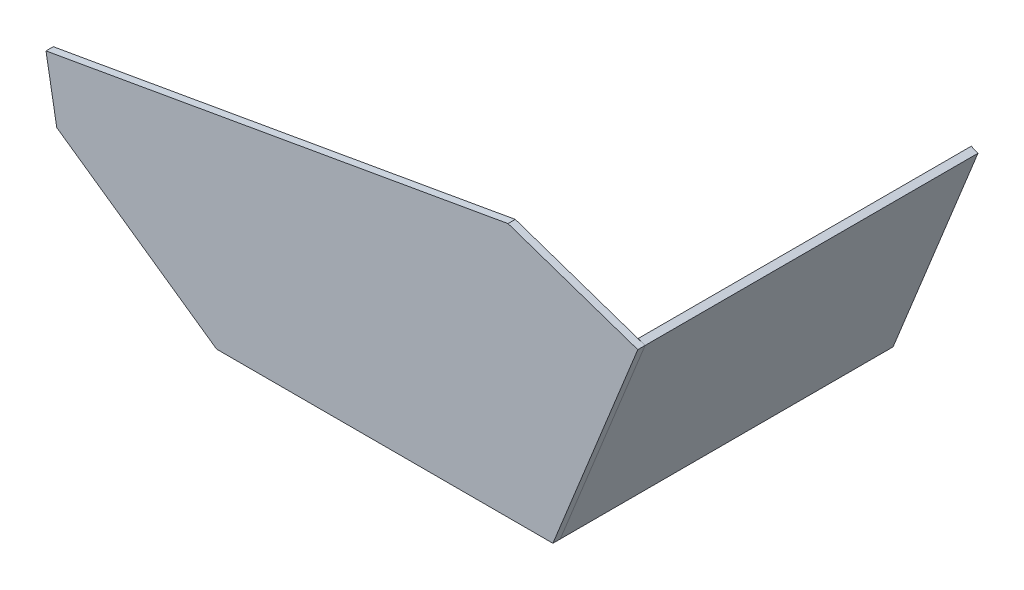
SolidWorks part; units mm, degrees
material "Melamine"
ref_plane "Front Plane" through (0, 0, 0) normal (0, 0, 1) x (1, 0, 0)
ref_plane "Top Plane" through (0, 0, 0) normal (0, 1, 0) x (1, 0, 0)
ref_plane "Right Plane" through (0, 0, 0) normal (1, 0, 0) x (0, 0, -1)
ref_axis "Axis1" through (0, 0, -14.8175) along (0, 0, 1)
sketch "Sketch1" plane through (0, 0, 0) normal (0, 0, 1) x (1, 0, 0)
  line L0 (-137.5, 0) -> (137.5, 0) construction
  line L1 (-137.5, 0) -> (-301.3304, 114.7153) construction
  line L4 (-148.5709, 0) -> (-304.9726, 109.5137) construction
  line L5 (-304.9726, 109.5137) -> (-301.3304, 114.7153) construction
  line L11 (137.5, 0) -> (144.3487, 0)
  line L12 (137.5, 0) -> (212.4213, 185.4368) construction
  line L14 (144.3487, 0) -> (218.3089, 183.058)
  line L15 (218.3089, 183.058) -> (212.4213, 185.4368)
  line L16 (212.4213, 185.4368) -> (137.5, 0)
  line L17 (-137.5, 0) -> (-148.5709, 0) construction
  point P4 (0, 0)
  dimension "D1" = 35
  dimension "D2" = 275
  dimension "D4" = 200
  dimension "D6" = 6.35
  dimension "D7" = 68
  dimension "D8" = 200
  dimension "D9" = 6.35
extrude "Boss-Extrude1" add sketch "Sketch1" along normal blind 290
sketch "Sketch2" plane through (0, 0, 290) normal (0, 0, 1) x (1, 0, 0)
  line L1 (-297.2025, 150.6805) -> (105.2664, 221.6466)
  line L3 (144.3487, 0) -> (-148.5709, 0)
  line L4 (-148.5709, 0) -> (-287.8267, 97.508) construction
  line L5 (144.3487, 0) -> (218.3089, 183.058)
  line L7 (-287.8267, 97.508) -> (-297.2025, 150.6805)
  line L8 (-287.8267, 97.508) -> (-284.1845, 102.7096) construction
  line L9 (218.3089, 183.058) -> (105.2664, 221.6466)
  line L10 (144.3487, 0) -> (105.2664, 221.6466) construction
  line L11 (-287.8267, 97.508) -> (-148.5709, 0)
  line L13 (-148.5709, 0) -> (-137.5, 0) construction
  line L14 (-287.8267, 97.508) -> (-148.5709, 0) construction
  line L15 (-284.1845, 102.7096) -> (-137.5, 0) construction
  point P4 (0, 0)
  point P7 (110.1001, 222.4989)
  point P9 (0, 0)
  dimension "D1" = 10
  dimension "D2" = 200
  dimension "D3" = 6.35
  dimension "D4" = 35
  dimension "D5" = 170
  dimension "D6" = 275
extrude "Boss-Extrude2" add sketch "Sketch2" along normal blind 6.35 separate body
ref_plane "Plane1" through (0, 0, 0) normal (0.9848, 0.1736, 0) x (0, 0, 1)
